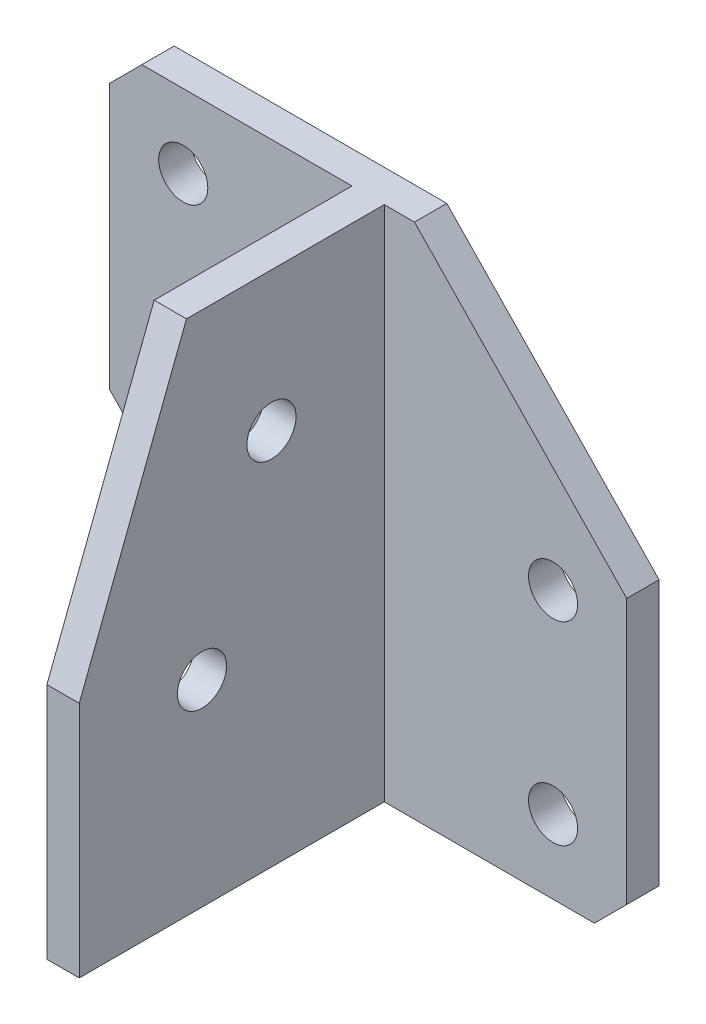
SolidWorks part; units mm, degrees
material "6061-T6 (SS)"
ref_plane "Front Plane" through (0, 0, 0) normal (0, 0, 1) x (1, 0, 0)
ref_plane "Top Plane" through (0, 0, 0) normal (0, 1, 0) x (1, 0, 0)
ref_plane "Right Plane" through (0, 0, 0) normal (1, 0, 0) x (0, 0, -1)
sketch "Sketch1" plane through (0, 0, 0) normal (0, 1, 0) x (1, 0, 0)
  line L1 (-2.3091, -33.8907) -> (0.8659, -33.8907)
  line L2 (-2.3091, -33.8907) -> (-2.3091, 1.0343)
  line L4 (0.8659, -33.8907) -> (0.8659, 1.0343)
  line L7 (-26.1216, 1.0343) -> (-2.3091, 1.0343)
  line L8 (-26.1216, 1.0343) -> (-26.1216, 4.2093)
  line L9 (-26.1216, 4.2093) -> (24.6784, 4.2093)
  line L10 (24.6784, 1.0343) -> (24.6784, 4.2093)
  line L15 (0.8659, 1.0343) -> (24.6784, 1.0343)
  point P0 (0, 0)
  point P6 (0, 2.6218)
  dimension "D1" = 3.175
  dimension "D2" = 3.175
  dimension "D3" = 38.1
  dimension "D4" = 3.175
  dimension "D5" = 50.8
extrude "Boss-Extrude1" add sketch "Sketch1" along normal blind 50.8
sketch "Sketch2" plane through (0, 0, -1.0343) normal (0, 0, 1) x (1, 0, 0)
  line L0 (3.8292, 50.8) -> (24.6784, 29.21)
  line L1 (0.8659, 50.8) -> (24.6784, 50.8) construction
  line L2 (24.6784, 50.8) -> (24.6784, 0) construction
  line L3 (-5.2724, 0) -> (-26.1216, 21.59)
  line L4 (-26.1216, 0) -> (-2.3091, 0) construction
  line L5 (-26.1216, 50.8) -> (-26.1216, 0) construction
  line L6 (24.6784, 29.21) -> (24.6784, 50.8)
  line L7 (24.6784, 50.8) -> (3.8292, 50.8)
  line L8 (-5.2724, 0) -> (-26.1216, 0)
  line L9 (-26.1216, 0) -> (-26.1216, 21.59)
  dimension "D1" = 44
  dimension "D2" = 44
  dimension "D3" = 21.59
  dimension "D4" = 21.59
extrude "Cut-Extrude1" cut sketch "Sketch2" against normal through all
sketch "Sketch4" plane through (0, 0, -1.0343) normal (0, 0, 1) x (1, 0, 0)
  line L0 (-0.7216, 50.8) -> (-0.7216, 0) construction
  line L1 (-2.3091, 50.8) -> (0.8659, 50.8) construction
  line L2 (-2.3091, 0) -> (0.8659, 0) construction
  line L3 (-26.1216, 50.8) -> (-2.3091, 50.8) construction
  line L5 (0.8659, 0) -> (24.6784, 0) construction
  circle A0 centre (-18.8826, 43.561) radius 2.413
  circle A1 centre (-18.8826, 24.511) radius 2.413
  circle A2 centre (17.4394, 7.239) radius 2.413
  circle A3 centre (17.4394, 26.289) radius 2.413
  dimension "D5" = 4.826
  dimension "D6" = 4.826
  dimension "D7" = 4.826
  dimension "D8" = 4.826
  dimension "D9" = 7.239
  dimension "D10" = 19.05
  dimension "D12" = 7.239
  dimension "D1" = 18.161
  dimension "D2" = 18.161
  dimension "D3" = 18.161
  dimension "D4" = 18.161
  dimension "D11" = 19.05
extrude "Cut-Extrude2" cut sketch "Sketch4" against normal through all
sketch "Sketch6" plane through (0.8659, 0, 0) normal (1, 0, 0) x (0, 0, -1)
  line L0 (-18.3967, 50.8) -> (-28.9269, 23.368)
  line L1 (-33.8907, 50.8) -> (1.0343, 50.8) construction
  line L2 (-28.9269, 23.368) -> (-28.9269, 0)
  line L3 (-33.8907, 0) -> (1.0343, 0) construction
  line L4 (-28.9269, 0) -> (-33.8907, 0)
  line L5 (-33.8907, 0) -> (-33.8907, 50.8)
  line L6 (-33.8907, 50.8) -> (-18.3967, 50.8)
  dimension "D1" = 15.494
  dimension "D2" = 69
  dimension "D3" = 23.368
extrude "Cut-Extrude4" cut sketch "Sketch6" against normal through all
sketch "Sketch5" plane through (0.8659, 0, 0) normal (1, 0, 0) x (0, 0, -1)
  line L0 (4.2093, 29.21) -> (4.2093, 0) construction
  line L2 (-16.8727, 19.3317) -> (-10.0458, 37.1164) construction
  line L11 (-28.9269, 23.368) -> (-18.3967, 50.8) construction
  circle A0 centre (-16.8727, 19.3317) radius 2.413
  circle A1 centre (-10.0458, 37.1164) radius 2.413
  dimension "D5" = 4.826
  dimension "D6" = 4.826
  dimension "D1" = 21.082
  dimension "D3" = 19.05
  dimension "D4" = 12.7
extrude "Cut-Extrude3" cut sketch "Sketch5" against normal through all
chamfer "Chamfer2" distance 3.175 angle 45 2 edges at (24.6784, 0, -2.6218) (-26.1216, 50.8, -2.6218)
